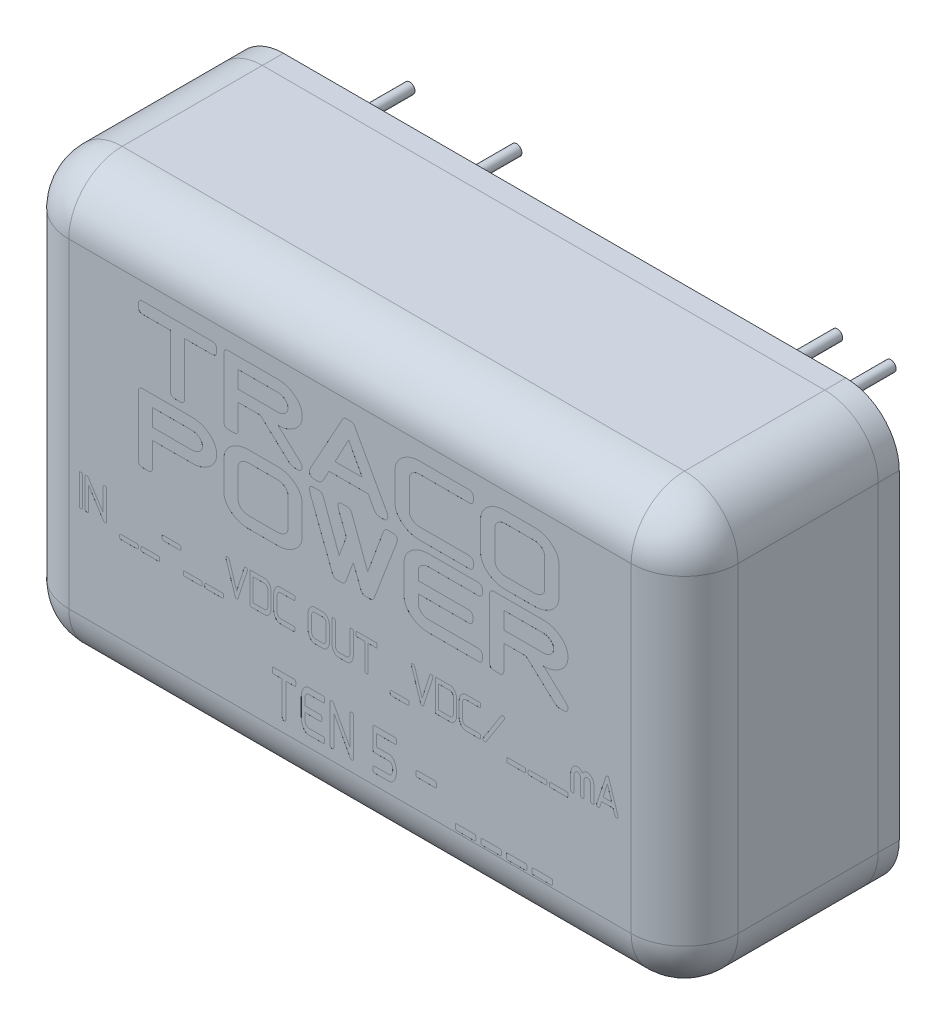
SolidWorks part; units mm, degrees
ref_plane "Спереди" through (0, 0, 0) normal (0, 0, 1) x (1, 0, 0)
ref_plane "Сверху" through (0, 0, 0) normal (0, 1, 0) x (1, 0, 0)
ref_plane "Справа" through (0, 0, 0) normal (1, 0, 0) x (0, 0, -1)
sketch "Эскиз1" plane through (0, 0, 0) normal (0, 0, 1) x (1, 0, 0)
  line L1 (-15.9, -10.15) -> (15.9, -10.15)
  line L2 (-15.9, -10.15) -> (-15.9, 10.15)
  line L3 (-15.9, 10.15) -> (15.9, 10.15)
  line L4 (15.9, -10.15) -> (15.9, 10.15)
  line L5 (-15.9, -10.15) -> (15.9, 10.15) construction
  line L6 (-15.9, 10.15) -> (15.9, -10.15) construction
  point P0 (0, 0)
  dimension "D1" = 31.8
  dimension "D2" = 20.3
extrude "Бобышка-Вытянуть1" add sketch "Эскиз1" along normal blind 1
sketch "Эскиз2" plane through (0, 0, 1) normal (0, 0, 1) x (1, 0, 0)
  line L1 (-15.9, -10.15) -> (15.9, -10.15)
  line L2 (-15.9, -10.15) -> (-15.9, 10.15)
  line L3 (-15.9, 10.15) -> (15.9, 10.15)
  line L4 (15.9, -10.15) -> (15.9, 10.15)
  line L5 (-15.9, -10.15) -> (15.9, 10.15) construction
  line L6 (-15.9, 10.15) -> (15.9, -10.15) construction
  point P0 (0, 0)
extrude "Бобышка-Вытянуть2" add sketch "Эскиз2" along normal blind 9.2 separate body
fillet "Скругление1" radius 2.54 8 edges at (0, -10.15, 10.2) (-15.9, 0, 10.2) (0, 10.15, 10.2) (15.9, 0, 10.2) (-15.9, 10.15, 5.6) (-15.9, -10.15, 5.6) (15.9, -10.15, 5.6) (15.9, 10.15, 5.6)
fillet "Скругление2" radius 2.54 4 edges at (15.9, -10.15, 0.5) (15.9, 10.15, 0.5) (-15.9, -10.15, 0.5) (-15.9, 10.15, 0.5)
sketch "Эскиз3" plane through (0, 0, 0) normal (0, 0, -1) x (-1, 0, 0)
  line L0 (-15.9, -7.61) -> (-15.9, 7.61) construction
  line L1 (-8.86, -7.62) -> (6.38, -7.62) construction
  line L2 (-8.86, -7.62) -> (-8.86, 7.62) construction
  line L3 (-8.86, 7.62) -> (6.38, 7.62) construction
  line L4 (6.38, -7.62) -> (6.38, 7.62) construction
  line L7 (-8.86, -7.62) -> (-11.4, -7.62) construction
  line L8 (-8.86, -7.62) -> (-8.86, 7.62) construction
  line L9 (-8.86, 7.62) -> (-11.4, 7.62) construction
  line L10 (-11.4, -7.62) -> (-11.4, 7.62) construction
  line L11 (6.38, -7.62) -> (11.46, -7.62) construction
  line L12 (6.38, -7.62) -> (6.38, 7.62) construction
  line L13 (6.38, 7.62) -> (11.46, 7.62) construction
  line L14 (11.46, -7.62) -> (11.46, 7.62) construction
  circle A0 centre (-11.4, -7.62) radius 0.25
  circle A1 centre (-8.86, -7.62) radius 0.25
  circle A2 centre (-11.4, 7.62) radius 0.25
  circle A3 centre (-8.86, 7.62) radius 0.25
  circle A4 centre (6.38, 7.62) radius 0.25
  circle A5 centre (11.46, 7.62) radius 0.25
  circle A6 centre (6.38, -7.62) radius 0.25
  circle A7 centre (11.46, -7.62) radius 0.25
  point P0 (0, 0)
  point P20 (-11.4, 0)
  dimension "D5" = 0.5
  dimension "D1" = 15.24
  dimension "D2" = 2.54
  dimension "D3" = 5.08
  dimension "D4" = 15.24
  dimension "D6" = 4.5
extrude "Бобышка-Вытянуть3" add sketch "Эскиз3" along normal blind 4.1 separate body
sketch "Эскиз4" plane through (0, 0, 10.2) normal (0, 0, 1) x (1, 0, 0)
  line L0 (-3.6882, -7.1) -> (9.76, -7.1) construction
  line L1 (-12.86, -3.2) -> (12.86, -3.2) construction
  line L4 (-10, 3.6) -> (10.1109, 3.6) construction
  line L5 (-13.36, 7.61) -> (-13.36, -7.61) construction
  line L6 (-10, 0) -> (10, 0) construction
  line L7 (13.36, -7.61) -> (13.36, 7.61) construction
  text T0 "TEN 5 - ____" font "Downlink" height 1.95
  text T1 "TRACO" font "Downlink" height 3.25
  text T2 "POWER" font "Downlink" height 3.25
  text T3 "IN __-__VDC OUT _VDC/___mA" font "Downlink" height 1.5
  point P6 (12.5412, -3.2465)
  point P7 (-12.8566, -3.2532)
  point P10 (9.8435, -7.0183)
  point P12 (0, 0)
  point P13 (12.5408, -3.2142)
  point P15 (10.1109, 0)
  point P16 (10.1109, 3.586)
  point P18 (10.1109, 3.6)
  point P19 (10.1109, 0)
  point P20 (0, 0)
  point P21 (0, 0)
  point P22 (0, 0)
  point P23 (0, 0)
  point P24 (-13.36, -3.2118)
  point P25 (-12.9802, -3.2)
  point P27 (13.36, -3.2118)
  point P28 (12.9695, -3.2)
  point P30 (9.7879, -7.0913)
  point P31 (-3.6882, -7.0913)
  point P34 (0, 0)
  point P36 (0, 0)
  dimension "D1" = 3.6
  dimension "D2" = 3.2
  dimension "D3" = 0.5
  dimension "D4" = 0.5
  dimension "D5" = 3.9
  dimension "D6" = 3.6
extrude "Вырез-Вытянуть1" cut sketch "Эскиз4" against normal blind 0.001
